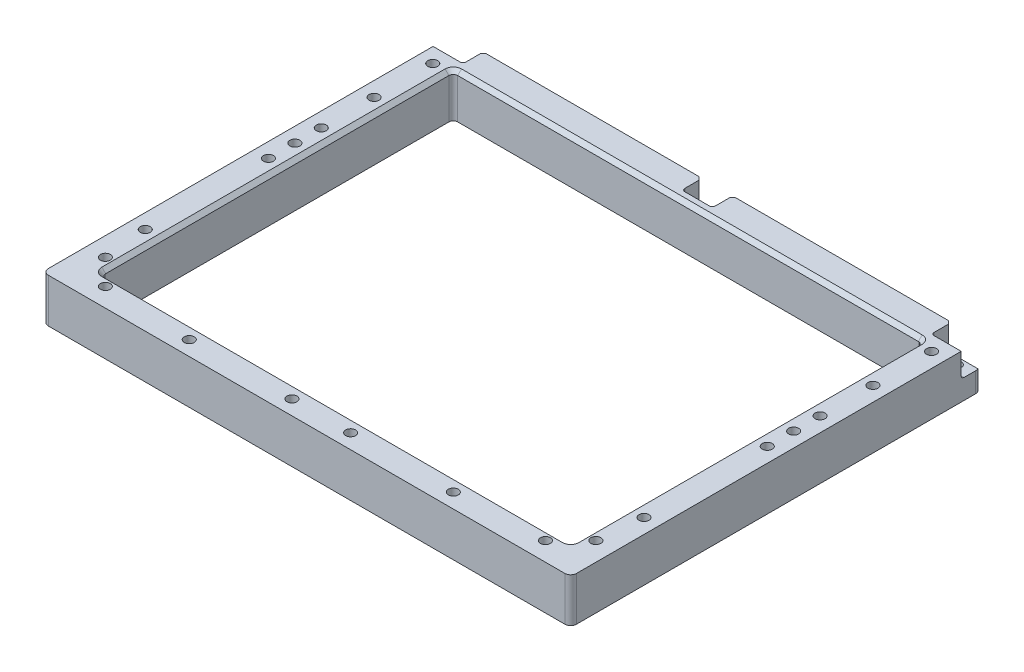
SolidWorks part; units mm, degrees
material "PLA"
ref_plane "Front Plane" through (0, 0, 0) normal (0, 0, 1) x (1, 0, 0)
ref_plane "Top Plane" through (0, 0, 0) normal (0, 1, 0) x (1, 0, 0)
ref_plane "Right Plane" through (0, 0, 0) normal (1, 0, 0) x (0, 0, -1)
sketch "Sketch1" plane through (0, 0, 0) normal (0, 1, 0) x (1, 0, 0)
  line L1 (-114.3, 88.9) -> (114.3, 88.9)
  line L2 (-114.3, 88.9) -> (-114.3, -88.9)
  line L3 (-114.3, -88.9) -> (114.3, -88.9)
  line L4 (114.3, 88.9) -> (114.3, -88.9)
  line L5 (-114.3, 88.9) -> (114.3, -88.9) construction
  line L6 (-114.3, -88.9) -> (114.3, 88.9) construction
  line L7 (-101.6, 76.2) -> (101.6, 76.2)
  line L8 (-101.6, 76.2) -> (-101.6, -76.2)
  line L9 (-101.6, -76.2) -> (101.6, -76.2)
  line L10 (101.6, 76.2) -> (101.6, -76.2)
  line L11 (-101.6, 76.2) -> (101.6, -76.2) construction
  line L12 (-101.6, -76.2) -> (101.6, 76.2) construction
  point P0 (0, 0)
  point P6 (0, 0)
  dimension "D1" = 177.8
  dimension "D2" = 152.4
  dimension "D3" = 228.6
  dimension "D4" = 203.2
extrude "Boss-Extrude1" add sketch "Sketch1" along normal blind 19.05
sketch "Sketch2" plane through (0, 0, -88.9) normal (0, 0, -1) x (-1, 0, 0)
  line L0 (114.3, 19.05) -> (114.3, 8.636)
  line L1 (114.3, 19.05) -> (114.3, 0) construction
  line L2 (114.3, 8.636) -> (101.346, 8.636)
  line L3 (101.346, 8.636) -> (101.346, 19.05)
  line L4 (-114.3, 19.05) -> (114.3, 19.05) construction
  line L5 (101.346, 19.05) -> (114.3, 19.05)
  line L6 (0, 0) -> (0, 19.05) construction
  line L7 (-6.604, 19.05) -> (6.604, 19.05)
  line L8 (6.604, 19.05) -> (6.604, 8.636)
  line L9 (6.604, 8.636) -> (-6.604, 8.636)
  line L11 (-6.604, 19.05) -> (-6.604, 8.636)
  line L12 (-101.346, 19.05) -> (-114.3, 19.05)
  line L13 (-101.346, 8.636) -> (-101.346, 19.05)
  line L14 (-114.3, 8.636) -> (-101.346, 8.636)
  line L15 (-114.3, 19.05) -> (-114.3, 8.636)
  point P16 (0, 8.636)
  dimension "D1" = 10.414
  dimension "D2" = 12.954
  dimension "D3" = 10.414
  dimension "D4" = 13.208
extrude "Cut-Extrude1" cut sketch "Sketch2" against normal blind 8.763
sketch "Sketch3" plane through (0, 8.636, 0) normal (0, 1, 0) x (1, 0, 0)
  line L0 (0, 88.9) -> (0, 80.137) construction
  line L1 (6.604, 88.9) -> (-6.604, 88.9) construction
  line L2 (-6.604, 80.137) -> (6.604, 80.137) construction
  line L3 (-107.823, 80.137) -> (-107.823, 88.9) construction
  line L4 (-114.3, 80.137) -> (-101.346, 80.137) construction
  line L5 (-101.346, 88.9) -> (-114.3, 88.9) construction
  circle A0 centre (-107.823, 84.5185) radius 2.159
  circle A1 centre (0, 84.5185) radius 2.159
  circle A2 centre (107.823, 84.5185) radius 2.159
  dimension "D1" = 4.318
  dimension "D2" = 4.318
extrude "Cut-Extrude2" cut sketch "Sketch3" against normal blind 6.35
fillet "Fillet2" radius 1.27 11 edges at (101.346, 8.636, -84.5185) (107.823, 8.636, -80.137) (-6.604, 8.636, -84.5185) (0, 8.636, -80.137) (6.604, 8.636, -84.5185) (-107.823, 8.636, -80.137) (-101.346, 8.636, -84.5185) (-101.346, 13.843, -80.137) (-6.604, 13.843, -80.137) (6.604, 13.843, -80.137) (101.346, 13.843, -80.137)
chamfer "Chamfer1" distance 1.27 angle 45 11 edges at (-108.458, 8.636, -88.9) (-101.718, 9.008, -88.9) (-101.346, 14.478, -88.9) (-6.604, 14.478, -88.9) (-6.232, 9.008, -88.9) (0, 8.636, -88.9) (6.232, 9.008, -88.9) (6.604, 14.478, -88.9) (108.458, 8.636, -88.9) (101.718, 9.008, -88.9) (101.346, 14.478, -88.9)
sketch "Sketch4" plane through (0, 0, -88.9) normal (0, 0, -1) x (-1, 0, 0)
  line L0 (0, 0) -> (0, 19.05) construction
  line L1 (-114.3, 0) -> (114.3, 0) construction
  line L2 (5.334, 19.05) -> (-5.334, 19.05) construction
  circle A0 centre (-20.32, 9.525) radius 1.905
  circle A1 centre (-81.28, 9.525) radius 1.905
  circle A2 centre (81.28, 9.525) radius 1.905
  circle A3 centre (20.32, 9.525) radius 1.905
  dimension "D1" = 3.81
  dimension "D2" = 3.81
  dimension "D3" = 20.32
  dimension "D4" = 81.28
  dimension "D5" = 9.525
  dimension "D6" = 9.525
extrude "Cut-Extrude3" cut sketch "Sketch4" against normal blind 7.112
sketch "Sketch5" plane through (0, 19.05, 0) normal (0, 1, 0) x (1, 0, 0)
  line L0 (-114.3, 80.137) -> (-114.3, -88.9) construction
  line L1 (-114.3, -88.9) -> (114.3, -88.9) construction
  line L2 (0, 0) -> (0, -50000) construction
  circle A0 centre (-95.25, -80.772) radius 2.159
  circle A1 centre (-106.172, -69.85) radius 2.159
  circle A2 centre (106.172, -69.85) radius 2.159
  circle A3 centre (95.25, -80.772) radius 2.159
  dimension "D1" = 4.318
  dimension "D2" = 4.318
  dimension "D3" = 8.128
  dimension "D4" = 8.128
  dimension "D5" = 19.05
  dimension "D6" = 19.05
extrude "Cut-Extrude4" cut sketch "Sketch5" against normal blind 7.112
fillet "Fillet3" radius 1.905 4 edges at (-101.6, 9.525, 76.2) (101.6, 9.525, 76.2) (101.6, 9.525, -76.2) (-101.6, 9.525, -76.2)
sketch "Sketch6" plane through (0, 19.05, 0) normal (0, 1, 0) x (1, 0, 0)
  line L0 (114.3, -88.9) -> (114.3, 80.137) construction
  line L1 (-99.695, -76.2) -> (99.695, -76.2) construction
  line L2 (101.6, -74.295) -> (101.6, 74.295) construction
  line L3 (0, 0) -> (0, -76.2) construction
  circle A0 centre (107.95, -50.8) radius 2.159
  circle A1 centre (107.95, 2.54) radius 2.159
  circle A2 centre (107.95, 13.97) radius 2.159
  circle A3 centre (107.95, 25.4) radius 2.159
  circle A4 centre (-107.95, 25.4) radius 2.159
  circle A5 centre (-107.95, 13.97) radius 2.159
  circle A6 centre (-107.95, 2.54) radius 2.159
  circle A7 centre (-107.95, -50.8) radius 2.159
  dimension "D1" = 4.318
  dimension "D4" = 4.318
  dimension "D5" = 4.318
  dimension "D6" = 4.318
  dimension "D2" = 6.35
  dimension "D7" = 78.74
  dimension "D8" = 90.17
  dimension "D9" = 101.6
  dimension "D10" = 6.35
  dimension "D11" = 6.35
  dimension "D12" = 6.35
extrude "Motor_Mount_Holes" cut sketch "Sketch6" against normal blind 7.112
chamfer "Chamfer2" distance 1.651 angle 45 8 edges at (-101.6, 19.05, 0) (-101.042, 19.05, 75.642) (-101.042, 19.05, -75.642) (0, 19.05, 76.2) (0, 19.05, -76.2) (101.042, 19.05, 75.642) (101.042, 19.05, -75.642) (101.6, 19.05, 0)
sketch "Sketch7" plane through (0, 19.05, 0) normal (0, 1, 0) x (1, 0, 0)
  line L0 (0, 0) -> (0, -88.9) construction
  line L1 (-114.3, -88.9) -> (114.3, -88.9) construction
  line L2 (-12.7, -76.2) -> (-12.7, -88.9) construction
  line L4 (-99.695, -76.2) -> (99.695, -76.2) construction
  circle A0 centre (-12.7, -82.55) radius 2.159
  circle A1 centre (12.7, -82.55) radius 2.159
  dimension "D1" = 4.318
  dimension "D2" = 12.7
extrude "RearBrace_MountHoles" cut sketch "Sketch7" against normal blind 7.112
sketch "Sketch8" plane through (0, 19.05, 0) normal (0, 1, 0) x (1, 0, 0)
  line L0 (114.3, 60.96) -> (101.6, 60.96) construction
  line L1 (114.3, -88.9) -> (114.3, 80.137) construction
  line L2 (101.6, -74.295) -> (101.6, 74.295) construction
  line L3 (107.95, 60.96) -> (107.95, 73.66) construction
  line L4 (-99.695, -76.2) -> (99.695, -76.2) construction
  line L5 (0, 0) -> (0, -88.9) construction
  line L6 (-114.3, -88.9) -> (114.3, -88.9) construction
  line L7 (-107.95, 60.96) -> (-107.95, 73.66) construction
  line L8 (-114.3, 60.96) -> (-101.6, 60.96) construction
  circle A0 centre (107.95, 73.66) radius 2.159
  circle A1 centre (107.95, 48.26) radius 2.159
  circle A2 centre (-107.95, 48.26) radius 2.159
  circle A3 centre (-107.95, 73.66) radius 2.159
  dimension "D1" = 4.318
  dimension "D2" = 25.4
  dimension "D3" = 137.16
extrude "SideBrace_MountHoles" cut sketch "Sketch8" against normal blind 7.112
sketch "Sketch9" plane through (0, 19.05, 0) normal (0, 1, 0) x (1, 0, 0)
  line L0 (0, -88.9) -> (0, -76.2) construction
  line L1 (-114.3, -88.9) -> (114.3, -88.9) construction
  line L2 (-99.695, -76.2) -> (99.695, -76.2) construction
  line L3 (0, -82.55) -> (-57.15, -82.55) construction
  circle A0 centre (-57.15, -82.55) radius 2.159
  circle A1 centre (57.15, -82.55) radius 2.159
  dimension "D1" = 4.318
  dimension "D2" = 114.3
extrude "BatteryMount_Holes" cut sketch "Sketch9" against normal blind 7.112
fillet "Fillet4" radius 2.54 4 edges at (-114.3, 3.683, -88.9) (114.3, 3.683, -88.9) (-114.3, 9.525, 88.9) (114.3, 9.525, 88.9)
equation "\"D2@Sketch3\"=\"D1@Sketch3\""
equation "\"D2@Sketch5\"=\"D1@Sketch5\""
equation "\"D4@Sketch6\"=\"D1@Sketch6\""
equation "\"D5@Sketch6\"=\"D1@Sketch6\""
equation "\"D6@Sketch6\"=\"D1@Sketch6\""
equation "\"D10@Sketch6\"=\"D2@Sketch6\""
equation "\"D11@Sketch6\"=\"D2@Sketch6\""
equation "\"D12@Sketch6\"=\"D2@Sketch6\""
equation "\"D1@Sketch2\"=\"D3@Sketch2\""
